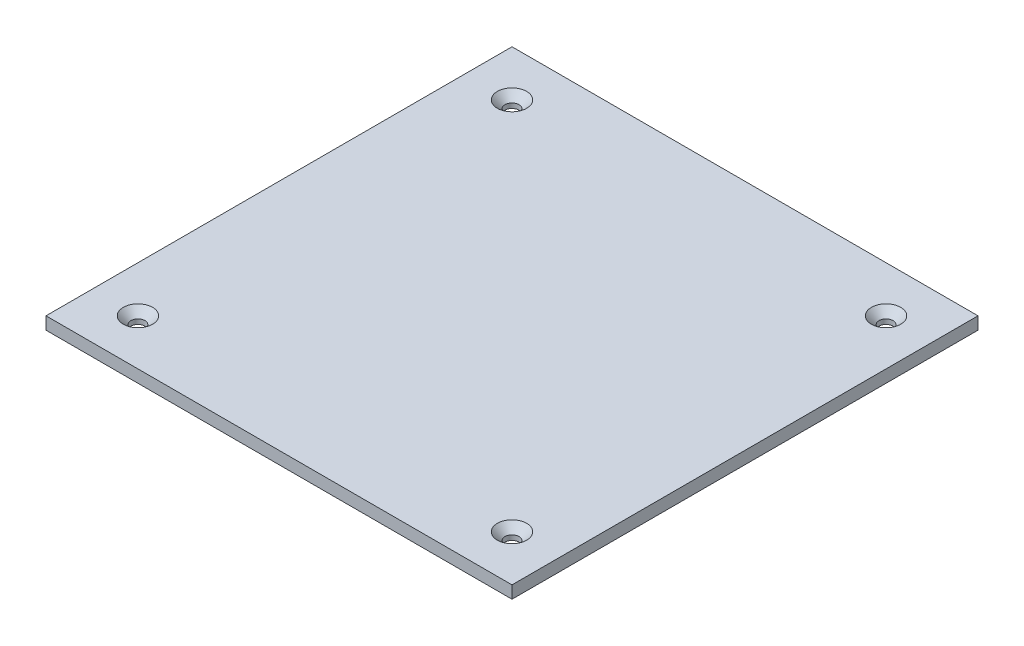
SolidWorks part; units mm, degrees
material "1060 Alloy"
ref_plane "Front Plane" through (0, 0, 0) normal (0, 0, 1) x (1, 0, 0)
ref_plane "Top Plane" through (0, 0, 0) normal (0, 1, 0) x (1, 0, 0)
ref_plane "Right Plane" through (0, 0, 0) normal (1, 0, 0) x (0, 0, -1)
sketch "Sketch1" plane through (0, 0, 0) normal (0, 1, 0) x (1, 0, 0)
  line L0 (74.75, -74.75) -> (-74.75, 74.75) construction
  line L1 (-74.75, 74.75) -> (74.75, 74.75)
  line L2 (-74.75, 74.75) -> (-74.75, -74.75)
  line L3 (-74.75, -74.75) -> (74.75, -74.75)
  line L4 (74.75, 74.75) -> (74.75, -74.75)
  dimension "D1" = 149.5
  dimension "D2" = 149.5
sheet metal parameters "Sheet-Metal1" thickness 4 parameters "D1"=5
base flange "Base-Flange1" sketch "Sketch1" thickness 4 reverse thickness direction no parameters "D1"=5
sketch "Sketch4" plane through (0, 0, 0) normal (0, 1, 0) x (1, 0, 0)
  line L0 (-60, -60) -> (60, 60) construction
  line L1 (60, 60) -> (-60, 60) construction
  line L2 (60, 60) -> (60, -60) construction
  line L3 (60, -60) -> (-60, -60) construction
  line L4 (-60, 60) -> (-60, -60) construction
  line L5 (60, 60) -> (59.4706, 59.7353) construction
  dimension "D1" = 120
hole_wizard "CSK for M4 Flat Head Machine Screw1" positions "Sketch6" profile "Sketch5" countersink size "M4" standard "ANSI Metric" end condition through all
sketch "Sketch6" plane through (0, 0, 0) normal (0, 1, 0) x (1, 0, 0)
  point P0 (60, 60)
  point P3 (-60, 60)
  point P6 (-60, -60)
  point P9 (60, -60)
sketch "Sketch5" plane through (60, 0, -60) normal (1, 0, 0) x (0, 0, 1)
  line L0 (0, 0) -> (0, 4)
  line L1 (0, 4) -> (2.25, 4)
  line L2 (2.25, 4) -> (2.25, 2.45)
  line L3 (2.25, 2.45) -> (4.7, 0)
  line L5 (4.7, 0) -> (0, 0)
  line L6 (-2.25, 2.45) -> (-4.7, 0) construction
  line L11 (0, -6.35) -> (0, 107.95) construction
  dimension "Thru Hole Dia." = 4.5
  dimension "Thru Hole Depth" = 4
  dimension "Near C'Sink Dia." = 9.4
  dimension "Near C'Sink Angle" = 90
flat pattern "Flat-Pattern1" [suppressed]
sketch "Bend-Lines1" plane through (0, 0, 0) normal (0, 1, 0) x (1, 0, 0)
sketch3d "Bounding-Box1" [suppressed]
  line L0 (74.75, -74.75, 0) -> (-74.75, -74.75, 0) construction
  line L1 (74.75, 74.75, 0) -> (-74.75, 74.75, 0) construction
  line L2 (74.75, -74.75, 0) -> (74.75, 74.75, 0) construction
  line L3 (-74.75, -74.75, 0) -> (-74.75, 74.75, 0) construction
